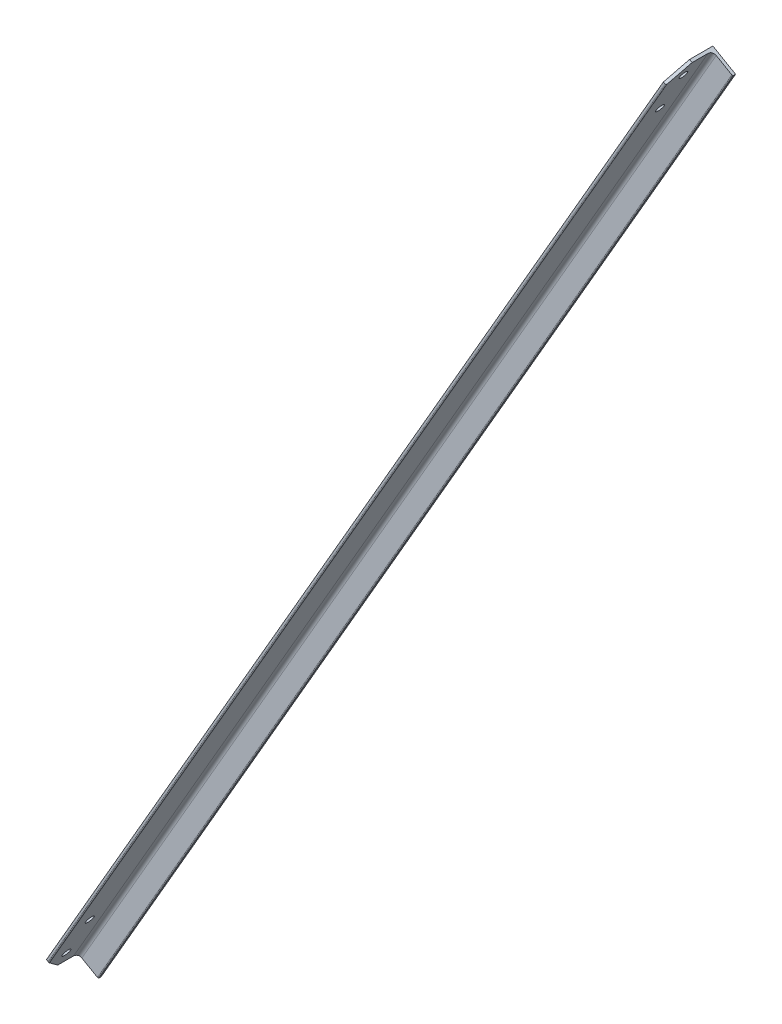
SolidWorks part; units mm, degrees
material "普通碳钢"
ref_plane "前视基准面" through (0, 0, 0) normal (0, 0, 1) x (1, 0, 0)
ref_plane "上视基准面" through (0, 0, 0) normal (0, 1, 0) x (1, 0, 0)
ref_plane "右视基准面" through (0, 0, 0) normal (1, 0, 0) x (0, 0, -1)
sketch "草图1" plane through (0, 0, 0) normal (0, 0, 1) x (1, 0, 0)
  line L0 (0, 0) -> (1090, 1887.9354) construction
  line L1 (0, 0) -> (171.8941, 0) construction
  line L2 (1090, 1887.9354) -> (0, 0)
  dimension "D1" = 60
  dimension "D2" = 2180
other "不等边角钢 70X45X5(1)"
ref_plane "基准面1" through (1090, 1887.9354, 0) normal (-0.5, -0.866, 0) x (0.866, -0.5, 0)
sketch "草图11" plane through (1090, 1887.9354, 0) normal (-0.5, -0.866, 0) x (0.866, -0.5, 0)
  line L0 (0, 70) -> (0, 0)
  line L1 (0, 0) -> (45, 0)
  line L2 (45, 0) -> (45, 3.33)
  line L3 (43.33, 5) -> (12.5, 5)
  line L4 (5, 12.5) -> (5, 68.33)
  line L5 (3.33, 70) -> (0, 70)
  arc A0 (12.5, 5) -> (5, 12.5) centre (12.5, 12.5) cw
  arc A1 (45, 3.33) -> (43.33, 5) centre (43.33, 3.33) ccw
  arc A2 (5, 68.33) -> (3.33, 70) centre (3.33, 68.33) ccw
  point P8 (5, 70)
  point P9 (0, 70)
  point P10 (0, 0)
  point P11 (45, 0)
  point P12 (45, 5)
  point P16 (45, 5)
  point P19 (5, 70)
  point P20 (0, 0)
  dimension "D5" = 7.5
  dimension "D6" = 1.67
  dimension "D1" = 45
  dimension "D2" = 70
  dimension "D3" = 5
  dimension "D4" = 5
sketch "草图12" plane through (0, 0, 0) normal (-0.866, 0.5, 0) x (0, 0, 1)
  line L0 (40, 0) -> (40, 182.7203) construction
  line L1 (70, 0) -> (0, 0) construction
  line L2 (70, 0) -> (70, 2180) construction
  line L3 (118.7853, 30) -> (40, 30) construction
  line L4 (118.7853, 110) -> (40, 110) construction
  circle A0 centre (40, 30) radius 7
  circle A1 centre (40, 110) radius 7
  dimension "D3" = 80
  dimension "D4" = 14
  dimension "D5" = 14
  dimension "D1" = 30
  dimension "D2" = 30
extrude "切除-拉伸1" cut sketch "草图12" against normal up to next
sketch "草图13" plane through (0, 0, 0) normal (-0.866, 0.5, 0) x (0, 0, 1)
  line L1 (40.0047, 2150) -> (40.0047, 2070) construction
  line L2 (70, 0) -> (70, 2180) construction
  line L3 (40.0047, 2150) -> (66.8756, 2150) construction
  line L4 (40.0047, 2070) -> (60.9865, 2070) construction
  line L5 (70, 2180) -> (0, 2180) construction
  circle A0 centre (40.0047, 2070) radius 7
  circle A1 centre (40.0047, 2150) radius 7
  dimension "D1" = 29.9953
  dimension "D2" = 30
  dimension "D3" = 80
extrude "切除-拉伸2" cut sketch "草图13" against normal up to next
chamfer "倒角1" distance 30 1 edges at (1091.4419, 1887.1029, 70)
chamfer "倒角2" distance 30 1 edges at (1.4419, -0.8325, 70)
